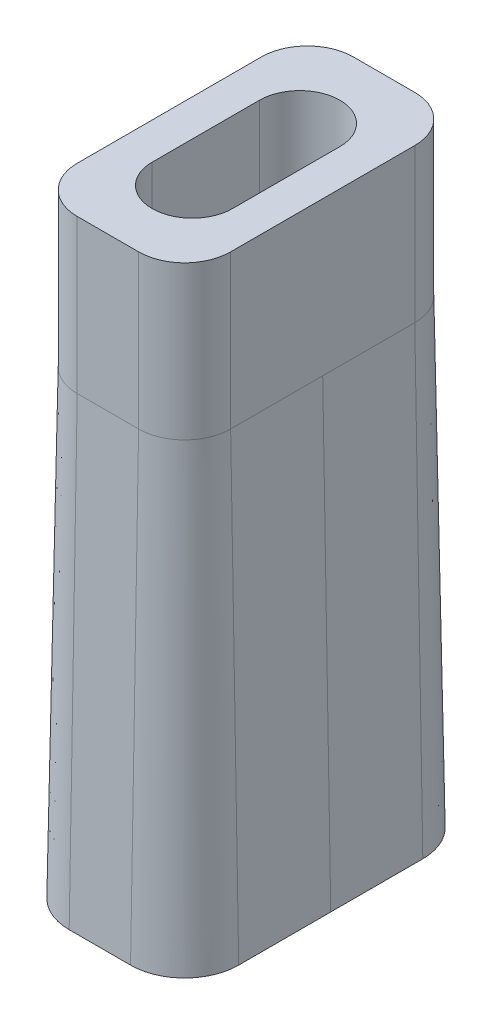
SolidWorks part; units mm, degrees
material "K110"
ref_plane "Front Plane" through (0, 0, 0) normal (0, 0, 1) x (1, 0, 0)
ref_plane "Top Plane" through (0, 0, 0) normal (0, 1, 0) x (1, 0, 0)
ref_plane "Right Plane" through (0, 0, 0) normal (1, 0, 0) x (0, 0, -1)
sketch "Sketch1" plane through (0, 0, 0) normal (0, 1, 0) x (1, 0, 0)
  line L3 (0, -3.5) -> (0, 3.5) construction
  line L4 (-2.62, -3.5) -> (-2.62, 3.5) construction
  line L5 (2.62, -3.5) -> (2.62, 3.5) construction
  line L6 (-2, -9) -> (2, -9)
  line L7 (-5, -6) -> (-5, 6)
  line L8 (-2, 9) -> (2, 9)
  line L9 (5, -6) -> (5, 6)
  line L10 (-5, -9) -> (5, 9) construction
  line L11 (-5, 9) -> (5, -9) construction
  arc A2 (-2.62, -3.5) -> (2.62, -3.5) centre (0, -3.5) ccw construction
  arc A3 (2.62, 3.5) -> (-2.62, 3.5) centre (0, 3.5) ccw construction
  arc A4 (-2, -9) -> (-5, -6) centre (-2, -6) cw
  arc A5 (2, -9) -> (5, -6) centre (2, -6) ccw
  arc A6 (2, 9) -> (5, 6) centre (2, 6) cw
  arc A7 (-5, 6) -> (-2, 9) centre (-2, 6) cw
  point P0 (0, 0)
  point P10 (0, 0)
  dimension "D1" = 7
  dimension "D3" = 2.62
  dimension "D5" = 3
  dimension "D2" = 18
  dimension "D4" = 10
extrude "Boss-Extrude1" add sketch "Sketch1" against normal blind 40
sketch "Sketch5" plane through (0, 0, 0) normal (0, 1, 0) x (1, 0, 0)
  line L0 (0, -3.5) -> (0, 3.5) construction
  line L1 (-2.62, -3.5) -> (-2.62, 3.5)
  line L2 (2.62, -3.5) -> (2.62, 3.5)
  arc A0 (-2.62, -3.5) -> (2.62, -3.5) centre (0, -3.5) ccw
  arc A1 (2.62, 3.5) -> (-2.62, 3.5) centre (0, 3.5) ccw
  point P4 (0, 0)
extrude "Cut-Extrude2" cut sketch "Sketch5" against normal up to next
sketch "Sketch6" plane through (0, 0, 0) normal (0, 0, 1) x (1, 0, 0)
  line L0 (5, -10) -> (5.5237, -40)
  line L1 (5, -40) -> (5, 0) construction
  line L2 (5.5237, -40) -> (5, -40)
  line L3 (5, -40) -> (5, -10)
  line L4 (5.884, 0) -> (-5.884, 0) construction
  dimension "D1" = 10
  dimension "D2" = 1
sweep "Sweep1" add profiles "Sketch6" path "Sketch1<3>"
sketch "Sketch1<3>" plane through (0, 0, 0) normal (0, 1, 0) x (1, 0, 0) same geometry as "Sketch1"
